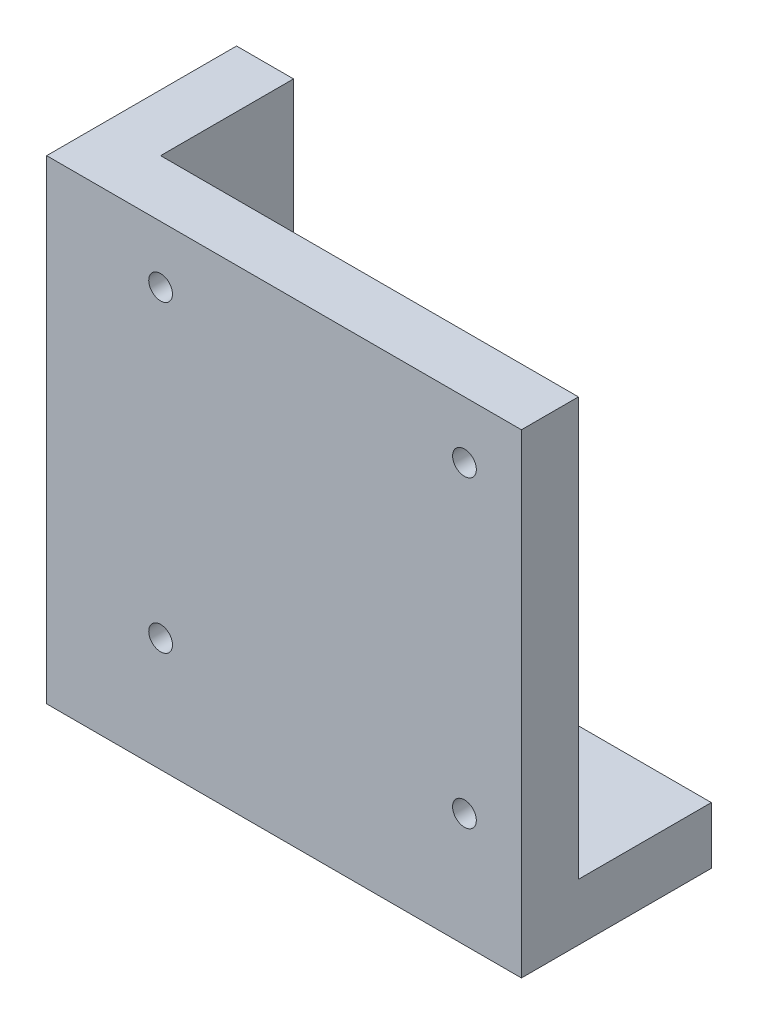
SolidWorks part; units mm, degrees
ref_plane "Front Plane" through (0, 0, 0) normal (0, 0, 1) x (1, 0, 0)
ref_plane "Top Plane" through (0, 0, 0) normal (0, 1, 0) x (1, 0, 0)
ref_plane "Right Plane" through (0, 0, 0) normal (1, 0, 0) x (0, 0, -1)
sketch "Sketch1" plane through (0, 0, 0) normal (0, 1, 0) x (1, 0, 0)
  line L1 (-21.3178, 5.6202) -> (28.6822, 5.6202)
  line L2 (-21.3178, 5.6202) -> (-21.3178, -14.3798)
  line L3 (-21.3178, -14.3798) -> (28.6822, -14.3798)
  line L4 (28.6822, 5.6202) -> (28.6822, -14.3798)
  dimension "D1" = 50
  dimension "D2" = 20
extrude "Boss-Extrude1" add sketch "Sketch1" along normal blind 6
sketch "Sketch2" plane through (0, 6, 0) normal (0, 1, 0) x (1, 0, 0)
  line L0 (-21.3178, -14.3798) -> (28.6822, -14.3798) construction
  line L1 (-21.3178, 5.6202) -> (-15.3178, 5.6202)
  line L2 (-21.3178, 5.6202) -> (-21.3178, -14.3798)
  line L3 (-21.3178, -14.3798) -> (-15.3178, -14.3798)
  line L4 (-15.3178, 5.6202) -> (-15.3178, -14.3798)
  dimension "D1" = 6
extrude "Boss-Extrude2" add sketch "Sketch2" along normal blind 44
sketch "Sketch3" plane through (0, 6, 0) normal (0, 1, 0) x (1, 0, 0)
  line L0 (-15.3178, -14.3798) -> (-15.3178, 5.6202) construction
  line L1 (28.6822, -14.3798) -> (-15.3178, -14.3798)
  line L2 (28.6822, -14.3798) -> (28.6822, -8.3798)
  line L3 (28.6822, -8.3798) -> (-15.3178, -8.3798)
  line L4 (-15.3178, -14.3798) -> (-15.3178, -8.3798)
  dimension "D1" = 6
extrude "Boss-Extrude3" add sketch "Sketch3" along normal blind 44
sketch "Sketch4" plane through (0, 0, 8.3798) normal (0, 0, -1) x (-1, 0, 0)
  line L0 (-28.6822, 50) -> (15.3178, 50) construction
  line L2 (-28.6822, 50) -> (-28.6822, 6) construction
  circle A0 centre (-22.6822, 44) radius 1.25
  circle A1 centre (9.3178, 44) radius 1.25
  circle A2 centre (-22.6822, 12) radius 1.25
  circle A3 centre (9.3178, 12) radius 1.25
  point P8 (0, 0)
  point P9 (0, 0)
  point P10 (0, 0)
  point P11 (0, 0)
  point P14 (-6.6822, 50)
  point P15 (0, 0)
  point P16 (0, 0)
  point P19 (0, 0)
  dimension "D1" = 32
  dimension "D2" = 32
  dimension "D3" = 32
  dimension "D4" = 32
  dimension "D5" = 16
  dimension "D6" = 6
  dimension "D7" = 6
extrude "Cut-Extrude1" cut sketch "Sketch4" against normal blind 44
